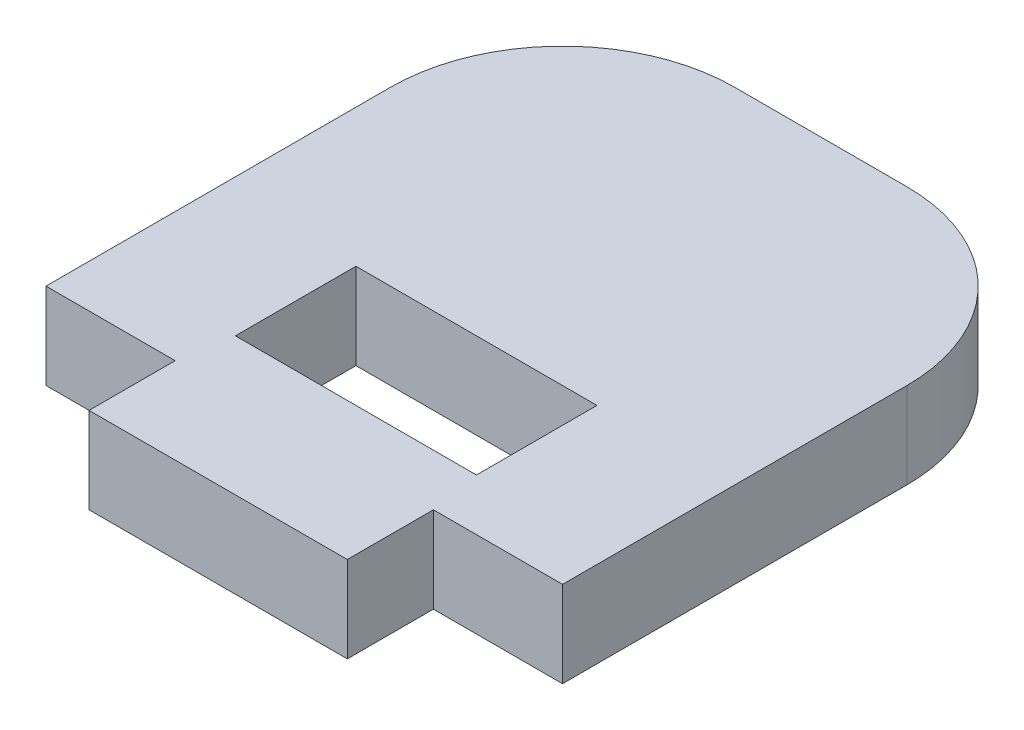
SolidWorks part; units mm, degrees
ref_plane "Front Plane" through (0, 0, 0) normal (0, 0, 1) x (1, 0, 0)
ref_plane "Top Plane" through (0, 0, 0) normal (0, 1, 0) x (1, 0, 0)
ref_plane "Right Plane" through (0, 0, 0) normal (1, 0, 0) x (0, 0, -1)
sketch "Sketch1" plane through (0, 0, 0) normal (0, 1, 0) x (1, 0, 0)
  line L0 (0, 41.275) -> (0, 3.175) construction
  line L1 (9.525, -3.175) -> (-9.525, -3.175)
  line L2 (9.525, -3.175) -> (9.525, 3.175)
  line L4 (-9.525, -3.175) -> (-9.525, 3.175)
  line L5 (9.525, -3.175) -> (-9.525, 3.175) construction
  line L6 (9.525, 3.175) -> (-9.525, -3.175) construction
  line L7 (-19.05, 3.175) -> (-9.525, 3.175)
  line L8 (-19.05, 3.175) -> (-19.05, 28.575)
  line L9 (-6.35, 41.275) -> (6.35, 41.275)
  line L10 (19.05, 3.175) -> (19.05, 28.575)
  line L11 (9.525, 3.175) -> (19.05, 3.175)
  arc A0 (6.35, 41.275) -> (19.05, 28.575) centre (6.35, 28.575) cw
  arc A1 (-19.05, 28.575) -> (-6.35, 41.275) centre (-6.35, 28.575) cw
  point P0 (0, 0)
  point P14 (19.05, 41.275)
  point P17 (-19.05, 41.275)
  dimension "D6" = 12.7
  dimension "D1" = 6.35
  dimension "D2" = 19.05
  dimension "D3" = 0
  dimension "D4" = 38.1
  dimension "D5" = 38.1
extrude "Boss-Extrude1" add sketch "Sketch1" along normal blind 6.35
sketch "Sketch2" plane through (0, 6.35, 0) normal (0, 1, 0) x (1, 0, 0)
  line L0 (-9.525, 3.175) -> (9.525, 3.175) construction
  line L1 (0, -3.175) -> (0, 3.175) construction
  line L2 (-9.525, -3.175) -> (9.525, -3.175) construction
  line L3 (0, 15.875) -> (0, 6.985) construction
  line L4 (-8.89, 15.875) -> (8.89, 15.875)
  line L5 (-8.89, 15.875) -> (-8.89, 6.985)
  line L6 (-8.89, 6.985) -> (8.89, 6.985)
  line L7 (8.89, 15.875) -> (8.89, 6.985)
  dimension "D1" = 0
  dimension "D2" = 17.78
  dimension "D3" = 8.89
  dimension "D4" = 3.81
extrude "Cut-Extrude1" cut sketch "Sketch2" against normal blind 6.35 contours L4 L7 L6 L5
